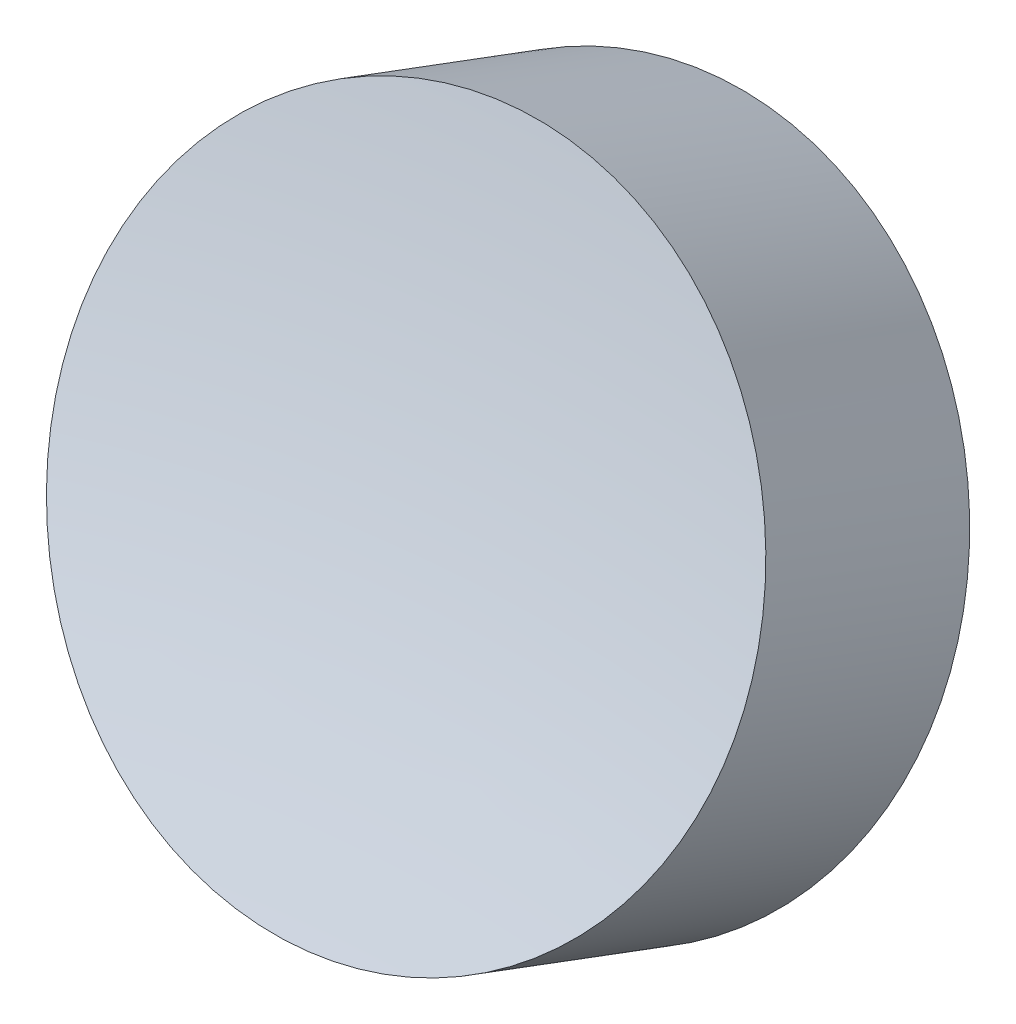
SolidWorks part; units mm, degrees
ref_plane "Plan de face" through (0, 0, 0) normal (0, 0, 1) x (1, 0, 0)
ref_plane "Plan de dessus" through (0, 0, 0) normal (0, 1, 0) x (1, 0, 0)
ref_plane "Plan de droite" through (0, 0, 0) normal (1, 0, 0) x (0, 0, -1)
ref_plane "Plan1" through (0, -1.4222, 0.591) normal (0, -0.9234, 0.3838) x (1, 0, 0)
sketch "Esquisse1" plane through (0, -1.4222, 0.591) normal (0, -0.9234, 0.3838) x (1, 0, 0)
  line L0 (-2.0387, 375.0019) -> (-2.0698, 374.5029)
  line L1 (-2.0387, 375.0019) -> (-3.2363, 355.8081) construction
  line L6 (9.8618, 365.0033) -> (10.8598, 364.941)
  line L7 (11.4825, 374.9216) -> (10.8598, 364.941)
  line L8 (9.8618, 365.0033) -> (10.4464, 374.3734)
  arc A1 (-2.0387, 375.0019) -> (11.4825, 374.9216) centre (5.4338, 494.7691) ccw
  arc A2 (-2.0698, 374.5029) -> (10.4464, 374.3734) centre (5.4338, 494.7691) ccw
  arc A3 (-2.0698, 374.5029) -> (11.5077, 374.4222) centre (5.4338, 494.7691) ccw construction
  dimension "D2" = 0.5
  dimension "D1" = 27
  dimension "D3" = 1
  dimension "D4" = 10
revolve "Révolution1" add sketch "Esquisse1" angle 360 about L0
ref_axis "Axe1" through (-17.2394, 48.9922, 121.9026) along (0.0623, 0.383, 0.9216)
